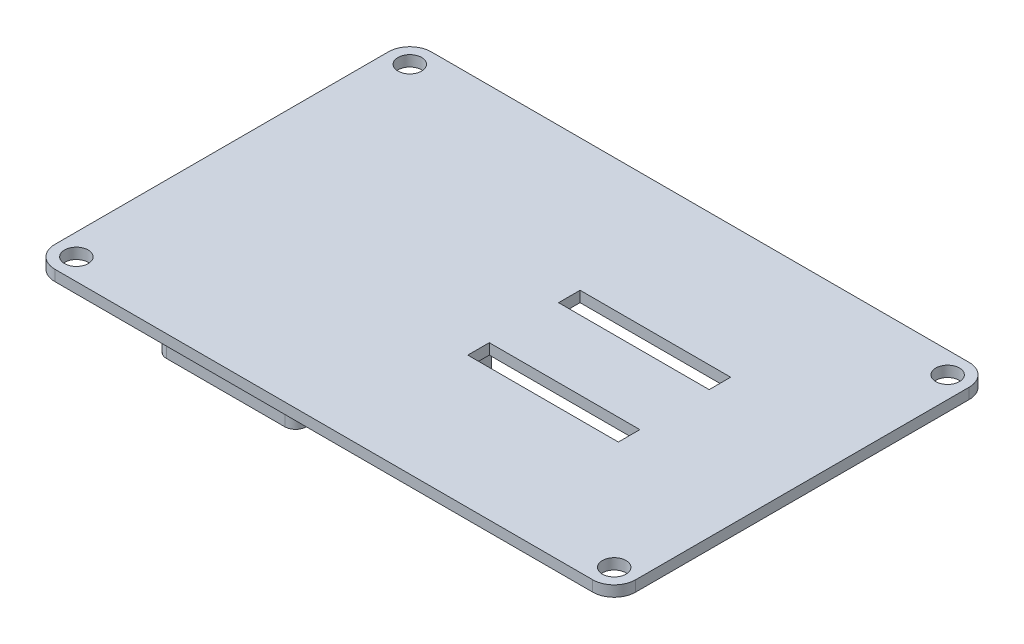
SolidWorks part; units mm, degrees
ref_plane "Front Plane" through (0, 0, 0) normal (0, 0, 1) x (1, 0, 0)
ref_plane "Top Plane" through (0, 0, 0) normal (0, 1, 0) x (1, 0, 0)
ref_plane "Right Plane" through (0, 0, 0) normal (1, 0, 0) x (0, 0, -1)
sketch "Sketch1" plane through (0, 0, 0) normal (0, 1, 0) x (1, 0, 0)
  line L1 (-68.58, -44.45) -> (68.58, -44.45)
  line L2 (-68.58, -44.45) -> (-68.58, 44.45)
  line L3 (-68.58, 44.45) -> (68.58, 44.45)
  line L4 (68.58, -44.45) -> (68.58, 44.45)
  line L5 (-68.58, -44.45) -> (68.58, 44.45) construction
  line L6 (-68.58, 44.45) -> (68.58, -44.45) construction
  point P0 (0, 0)
  dimension "D1" = 88.9
  dimension "D2" = 137.16
extrude "Boss-Extrude2" add sketch "Sketch1" along normal blind 2.54
sketch "Sketch2" plane through (0, 0, 0) normal (0, -1, 0) x (-1, 0, 0)
  line L1 (-63.5, 39.37) -> (63.5, 39.37)
  line L2 (-63.5, 39.37) -> (-63.5, -39.37)
  line L3 (-63.5, -39.37) -> (63.5, -39.37)
  line L4 (63.5, 39.37) -> (63.5, -39.37)
  line L5 (-63.5, 39.37) -> (63.5, -39.37) construction
  line L6 (-63.5, -39.37) -> (63.5, 39.37) construction
  circle A0 centre (63.5, 39.37) radius 2.794
  circle A1 centre (63.5, -39.37) radius 2.794
  circle A2 centre (-63.5, -39.37) radius 2.794
  circle A3 centre (-63.5, 39.37) radius 2.794
  point P0 (0, 0)
  dimension "D3" = 5.588
  dimension "D4" = 5.588
  dimension "D5" = 5.588
  dimension "D6" = 5.588
  dimension "D1" = 127
  dimension "D2" = 78.74
extrude "Cut-Extrude1" cut sketch "Sketch2" against normal blind 5.08 contours A0 | A1 | A2 | A3
sketch "Sketch8" plane through (0, 0, 0) normal (0, -1, 0) x (-1, 0, 0)
  line L1 (58.7259, -25.4) -> (25.7059, -25.4)
  line L2 (58.7259, -25.4) -> (58.7259, 27.94)
  line L3 (58.7259, 27.94) -> (25.7059, 27.94)
  line L4 (25.7059, -25.4) -> (25.7059, 27.94)
  line L5 (58.7259, -25.4) -> (25.7059, 27.94) construction
  line L6 (58.7259, 27.94) -> (25.7059, -25.4) construction
  point P0 (42.2159, 1.27)
  dimension "D1" = 33.02
  dimension "D2" = 53.34
sketch "Sketch9" plane through (0, 0, 0) normal (0, -1, 0) x (-1, 0, 0)
  line L0 (0, 44.45) -> (0, -44.45) construction
  line L1 (-68.58, 44.45) -> (68.58, 44.45) construction
  line L2 (68.58, -44.45) -> (-68.58, -44.45) construction
  line L3 (-68.58, 0) -> (68.58, 0) construction
  line L4 (-68.58, -44.45) -> (-68.58, 44.45) construction
  line L5 (68.58, 44.45) -> (68.58, -44.45) construction
  line L6 (-2.8155, -13.2599) -> (-2.8155, -8.1799)
  line L7 (-38.3755, 13.2599) -> (-2.8155, 13.2599)
  line L8 (-38.3755, 13.2599) -> (-38.3755, 8.1799)
  line L9 (-38.3755, 8.1799) -> (-2.8155, 8.1799)
  line L10 (-2.8155, 13.2599) -> (-2.8155, 8.1799)
  line L11 (-38.3755, 13.2599) -> (-2.8155, 8.1799) construction
  line L12 (-38.3755, 8.1799) -> (-2.8155, 13.2599) construction
  line L13 (-38.3755, -8.1799) -> (-2.8155, -8.1799)
  line L14 (-38.3755, -13.2599) -> (-38.3755, -8.1799)
  line L15 (-38.3755, -13.2599) -> (-2.8155, -13.2599)
  point P12 (-20.5955, 10.7199)
  dimension "D1" = 35.56
  dimension "D2" = 5.08
extrude "Cut-Extrude5" cut sketch "Sketch9" against normal blind 6.35
extrude "Boss-Extrude4" add sketch "Sketch8" along normal blind 21.59 separate body
shell "Shell4" thickness 2.54 removed face at (-42.2159, -21.59, -1.27)
sketch "Sketch13" plane through (0, 0, -27.94) normal (0, 0, -1) x (-1, 0, 0)
  line L0 (42.2159, 0) -> (42.2159, -21.59) construction
  line L1 (58.7259, 0) -> (25.7059, 0) construction
  line L2 (58.7259, -21.59) -> (25.7059, -21.59) construction
  line L3 (58.7259, -10.795) -> (25.7059, -10.795) construction
  line L4 (58.7259, -21.59) -> (58.7259, 0) construction
  line L5 (25.7059, -21.59) -> (25.7059, 0) construction
  line L7 (54.5224, -3.7461) -> (29.9095, -3.7461)
  line L8 (54.5224, -3.7461) -> (54.5224, -17.8439)
  line L9 (54.5224, -17.8439) -> (29.9095, -17.8439)
  line L10 (29.9095, -3.7461) -> (29.9095, -17.8439)
  line L11 (54.5224, -3.7461) -> (29.9095, -17.8439) construction
  line L12 (54.5224, -17.8439) -> (29.9095, -3.7461) construction
  point P12 (42.2159, -10.795)
extrude "Cut-Extrude6" cut sketch "Sketch13" against normal blind 5.08
fillet "Fillet5" radius 2.54 1 edges at (-29.9095, -17.8439, -26.67)
fillet "Fillet6" radius 2.54 1 edges at (-29.9095, -3.7461, -26.67)
fillet "Fillet7" radius 2.54 1 edges at (-54.5224, -3.7461, -26.67)
fillet "Fillet8" radius 2.54 1 edges at (-54.5224, -17.8439, -26.67)
fillet "Fillet1" radius 5.08 1 edges at (68.58, 1.27, 44.45)
fillet "Fillet2" radius 5.08 1 edges at (-68.58, 1.27, -44.45)
fillet "Fillet3" radius 5.08 1 edges at (-68.58, 1.27, 44.45)
fillet "Fillet4" radius 5.08 1 edges at (68.58, 1.27, -44.45)
fillet "Fillet9" radius 2.54 1 edges at (-25.7059, -10.795, -27.94)
fillet "Fillet10" radius 2.54 1 edges at (-25.7059, -10.795, 25.4)
fillet "Fillet11" radius 2.54 1 edges at (-58.7259, -10.795, 25.4)
fillet "Fillet12" radius 2.54 1 edges at (-58.7259, -10.795, -27.94)
sketch "Sketch17" plane through (0, 0, 0) normal (0, -1, 0) x (-1, 0, 0)
  line L0 (-68.58, 37.465) -> (68.58, 37.465) construction
  line L1 (-68.58, -39.37) -> (-68.58, 39.37) construction
  line L2 (68.58, 39.37) -> (68.58, -39.37) construction
  line L3 (-63.5, 44.45) -> (63.5, 44.45) construction
  line L5 (-44.6949, 37.465) -> (1.0251, 37.465) construction
  line L6 (-44.6949, 37.465) -> (-44.6949, -8.255) construction
  line L7 (-44.6949, -8.255) -> (1.0251, -8.255) construction
  line L8 (1.0251, 37.465) -> (1.0251, -8.255) construction
  line L9 (-44.6949, 37.465) -> (1.0251, -8.255) construction
  line L10 (-44.6949, -8.255) -> (1.0251, 37.465) construction
  circle A0 centre (1.0251, -8.255) radius 3.175
  circle A1 centre (1.0251, 37.465) radius 3.175
  circle A2 centre (-44.6949, 37.465) radius 3.175
  circle A3 centre (-44.6949, -8.255) radius 3.175
  point P12 (-21.8349, 14.605)
  point P18 (-44.6949, -8.255)
  point P19 (-44.6949, 37.465)
  point P20 (1.0251, 37.465)
  point P21 (1.0251, -8.255)
  point P22 (-44.6949, -8.255)
  point P23 (-44.6949, 37.465)
  point P24 (1.0251, -8.255)
  point P25 (1.0251, 37.465)
  dimension "D4" = 6.35
  dimension "D5" = 6.35
  dimension "D6" = 6.35
  dimension "D7" = 6.35
  dimension "D1" = 6.985
  dimension "D2" = 45.72
  dimension "D3" = 45.72
extrude "Boss-Extrude5" add sketch "Sketch17" along normal blind 7.62
sketch "Sketch18" plane through (0, -7.62, 0) normal (0, -1, 0) x (1, 0, 0)
  circle A0 centre (44.6949, 8.255) radius 1.651
  circle A1 centre (44.6949, -37.465) radius 1.651
  circle A2 centre (-1.0251, -37.465) radius 1.651
  circle A3 centre (-1.0251, 8.255) radius 1.651
  point P0 (-1.0251, 8.255)
  point P1 (-1.0251, -37.465)
  point P3 (44.6949, -37.465)
  point P5 (44.6949, 8.255)
  dimension "D1" = 3.302
  dimension "D2" = 3.302
  dimension "D3" = 3.302
  dimension "D4" = 3.302
extrude "Cut-Extrude7" cut sketch "Sketch18" against normal blind 5.08 draft 2 contours A0 | A1 | A2 | A3
ref_plane "Plane1" through (0, -21.59, 0) normal (0, -1, 0) x (-1, 0, 0)
